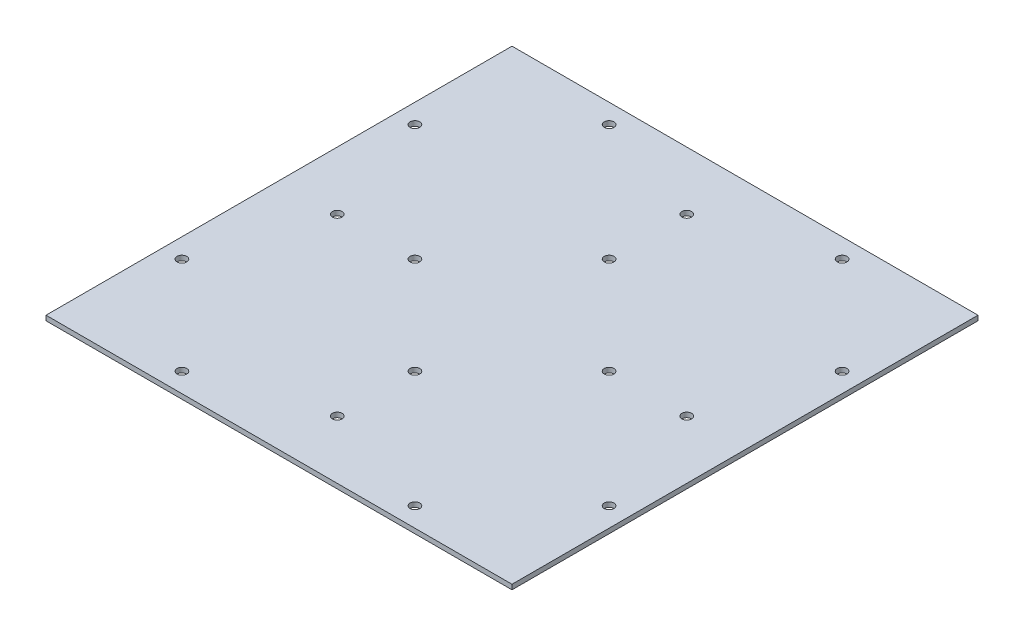
SolidWorks part; units mm, degrees
ref_plane "Front Plane" through (0, 0, 0) normal (0, 0, 1) x (1, 0, 0)
ref_plane "Top Plane" through (0, 0, 0) normal (0, 1, 0) x (1, 0, 0)
ref_plane "Right Plane" through (0, 0, 0) normal (1, 0, 0) x (0, 0, -1)
sketch "Sketch1" plane through (0, 0, 0) normal (0, 1, 0) x (1, 0, 0)
  line L1 (-152.4, 152.4) -> (152.4, 152.4)
  line L2 (-152.4, 152.4) -> (-152.4, -152.4)
  line L3 (-152.4, -152.4) -> (152.4, -152.4)
  line L4 (152.4, 152.4) -> (152.4, -152.4)
  line L5 (-152.4, 152.4) -> (152.4, -152.4) construction
  line L6 (-152.4, -152.4) -> (152.4, 152.4) construction
  point P0 (0, 0)
  dimension "D1" = 304.8
extrude "Boss-Extrude1" add sketch "Sketch1" along normal blind 3.175
sketch "Sketch2" plane through (0, 3.175, 0) normal (0, 1, 0) x (1, 0, 0)
  line L0 (152.4, 152.4) -> (-152.4, 152.4) construction
  circle A0 centre (0, 114.3) radius 3.175
  circle A1 centre (0, 63.5) radius 3.175
  point P6 (0, 152.4)
  dimension "D1" = 6.35
  dimension "D2" = 6.35
  dimension "D3" = 38.1
  dimension "D4" = 50.8
extrude "Cut-Extrude1" cut sketch "Sketch2" against normal up to next
sketch "Sketch3" plane through (0, 3.175, 0) normal (0, 1, 0) x (1, 0, 0)
  point P0 (0, 0)
ref_axis "Axis1" through (0, 3.175, 0) along (0, 1, 0)
pattern_circular "CirPattern1" count 4 over 360 about axis through (0, 3.175, 0) along (0, 1, 0) of "Cut-Extrude1"
sketch "Sketch4" plane through (0, 3.175, 0) normal (0, 1, 0) x (1, 0, 0)
  line L0 (152.4, 152.4) -> (-152.4, 152.4) construction
  line L1 (-76.2, 139.7) -> (76.2, 139.7) construction
  circle A0 centre (-76.2, 139.7) radius 3.175
  circle A1 centre (76.2, 139.7) radius 3.175
  point P6 (93.657, 215.9)
  point P7 (-62.1227, 215.9)
  point P8 (0, 139.7)
  dimension "D1" = 6.35
  dimension "D2" = 6.35
  dimension "D3" = 12.7
  dimension "D4" = 152.4
extrude "Cut-Extrude2" cut sketch "Sketch4" against normal up to next
pattern_circular "CirPattern2" count 4 over 360 about axis through (0, 3.175, 0) along (0, 1, 0) of "Cut-Extrude2"
